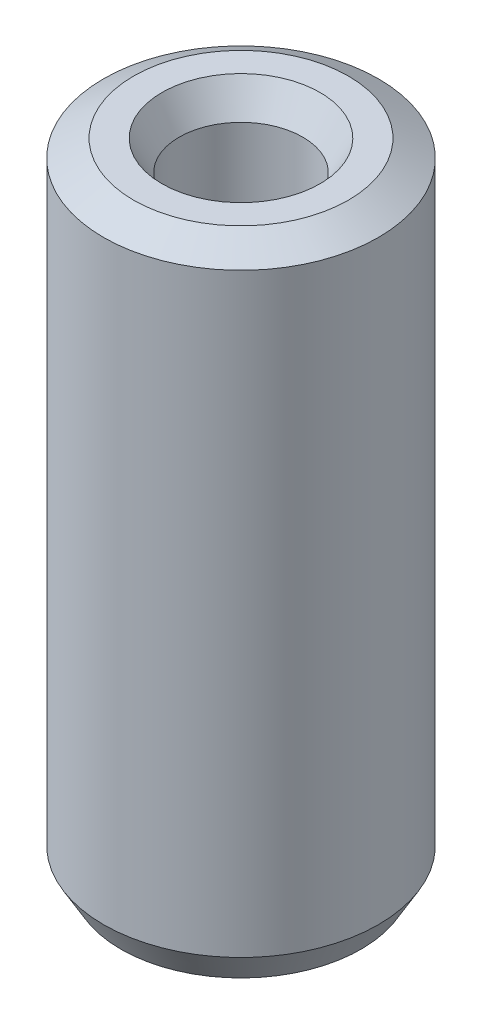
SolidWorks part; units mm, degrees
ref_plane "Front Plane" through (0, 0, 0) normal (0, 0, 1) x (1, 0, 0)
ref_plane "Top Plane" through (0, 0, 0) normal (0, 1, 0) x (1, 0, 0)
ref_plane "Right Plane" through (0, 0, 0) normal (1, 0, 0) x (0, 0, -1)
sketch "Sketch1" plane through (0, 0, 0) normal (0, 1, 0) x (1, 0, 0)
  circle A0 centre (0, 0) radius 7.5
  dimension "SLEEVE_OD" = 15
extrude "Boss-Extrude1" add sketch "Sketch1" along normal blind 35.0572
sketch "Sketch2" plane through (0, 0, 0) normal (0, 1, 0) x (1, 0, 0)
  circle A0 centre (0, 0) radius 3.3713
  dimension "BORE_D" = 6.7426
extrude "Cut-Extrude1" cut sketch "Sketch2" along normal through all
chamfer "Chamfer1" distance 0.9444 angle 60 4 edges at (0, 35.0572, 3.3713) (0, 0, 3.3713) (0, 0, 7.5) (0, 35.0572, 7.5) first distance on face at (0, 35.0572, 3.3713) first distance on face at (0, 0, 3.3713) first distance on face at (0, 35.0572, 7.5)
